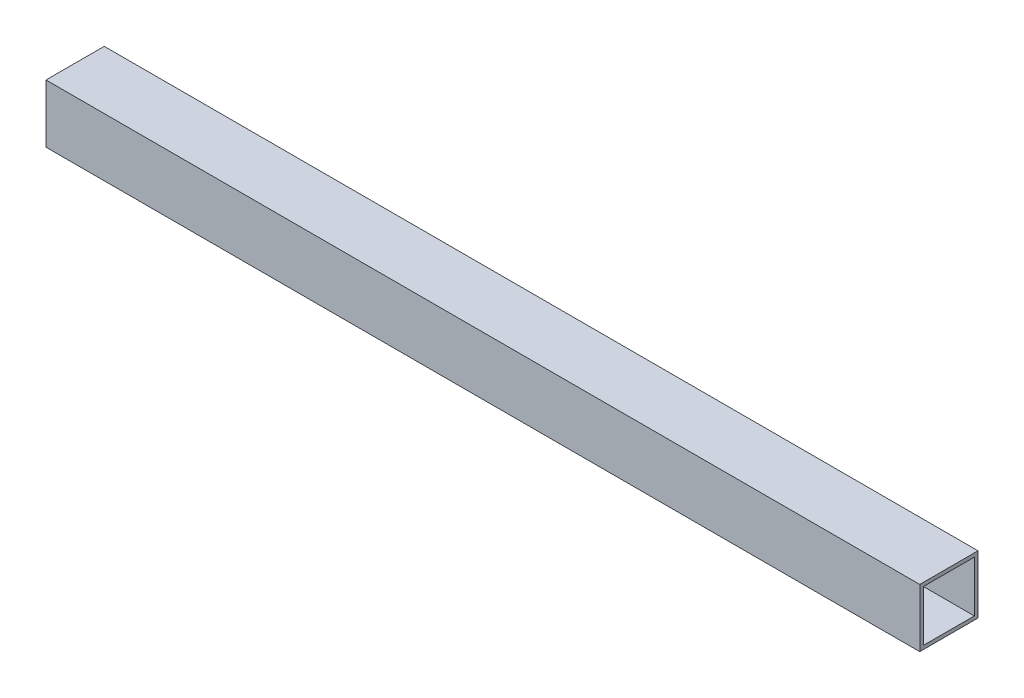
SolidWorks part; units mm, degrees
material "6061-T6 (SS)"
ref_plane "Front" through (0, 0, 0) normal (0, 0, 1) x (1, 0, 0)
ref_plane "Top" through (0, 0, 0) normal (0, 1, 0) x (1, 0, 0)
ref_plane "Right" through (0, 0, 0) normal (1, 0, 0) x (0, 0, -1)
sketch "Sketch1" plane through (0, 0, 0) normal (1, 0, 0) x (0, 0, -1)
  line L1 (-12.7, -12.7) -> (12.7, -12.7)
  line L2 (-12.7, -12.7) -> (-12.7, 12.7)
  line L3 (-12.7, 12.7) -> (12.7, 12.7)
  line L4 (12.7, -12.7) -> (12.7, 12.7)
  line L5 (-12.7, -12.7) -> (12.7, 12.7) construction
  line L6 (-12.7, 12.7) -> (12.7, -12.7) construction
  point P0 (0, 0)
  dimension "D1" = 25.4
extrude "Extrude-Thin1" add sketch "Sketch1" along normal blind 381 thin thin type one direction reverse wall 1.5875
